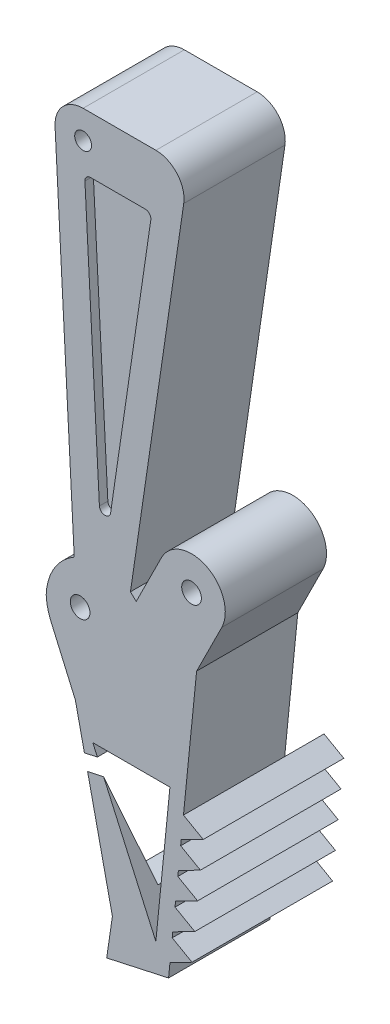
SolidWorks part; units mm, degrees
ref_plane "Front Plane" through (0, 0, 0) normal (0, 0, 1) x (1, 0, 0)
ref_plane "Top Plane" through (0, 0, 0) normal (0, 1, 0) x (1, 0, 0)
ref_plane "Right Plane" through (0, 0, 0) normal (1, 0, 0) x (0, 0, -1)
sketch "Sketch1" plane through (0, 0, 0) normal (0, 0, 1) x (1, 0, 0)
  line L1 (2.4995, -2.6404) -> (12.8102, 67.6069)
  line L2 (-7.4946, -2.2955) -> (-11.1898, 67.6069)
  line L3 (-11.1898, 67.6069) -> (12.8102, 67.6069)
  line L4 (-7.2953, -24.2105) -> (-0.7118, -54.2105)
  line L5 (-12.4946, -2.2955) -> (-12.4946, -12.2955)
  line L6 (-12.4946, -12.2955) -> (-7.2953, -24.2105)
  line L11 (2.4995, -2.6404) -> (3.5233, -3.6137)
  line L12 (3.5233, -3.6137) -> (7.9885, 5.334)
  line L13 (14.2607, -8.9719) -> (18.7258, -0.0241)
  line L15 (-12.4946, -2.2955) -> (-7.4946, -2.2955)
  line L16 (-0.7118, -54.2105) -> (-1.7284, -61.1363)
  line L17 (-1.7284, -61.1363) -> (9.2716, -58.7224)
  line L18 (9.2716, -58.7224) -> (14.2607, -8.9719)
  arc A0 (18.7258, -0.0241) -> (7.9885, 5.334) centre (13.3571, 2.655) ccw
  point P9 (0, 0)
  dimension "D15" = 12
  dimension "D1" = 10
  dimension "D2" = 71
  dimension "D3" = 70
  dimension "D4" = 24
  dimension "D5" = 5
  dimension "D6" = 10
  dimension "D7" = 13
  dimension "D8" = 30
  dimension "D9" = 7
  dimension "D10" = 11
  dimension "D11" = 50
  dimension "D12" = 10
  dimension "D13" = 10
  dimension "D14" = 12
extrude "Boss-Extrude1" add sketch "Sketch1" along normal blind 18
sketch "Sketch4" plane through (0, 0, 0) normal (0, 0, -1) x (-1, 0, 0)
  line L0 (0.7118, -54.2105) -> (-14.7329, -54.2105) construction
  line L1 (-7.0105, -54.2105) -> (-9.5176, -29.2105)
  line L2 (-9.5176, -29.2105) -> (4.2008, -29.2105)
  line L3 (4.2008, -29.2105) -> (-7.0105, -54.2105)
  line L4 (-9.2716, -58.7224) -> (-14.2607, -8.9719) construction
  dimension "D1" = 25
  dimension "D2" = 13.7184
  dimension "D3" = 2.7
extrude "Cut-Extrude1" cut sketch "Sketch4" against normal blind 25
sketch "Sketch5" plane through (0, 0, 18) normal (0, 0, 1) x (1, 0, 0)
  line L1 (9.5235, -56.2105) -> (9.9246, -52.2105)
  line L2 (9.2716, -58.7224) -> (14.2607, -8.9719) construction
  line L3 (9.9246, -52.2105) -> (13.4409, -54.2105)
  line L4 (9.5235, -56.2105) -> (13.4409, -54.2105)
  point P8 (9.7241, -54.2105)
  dimension "D1" = 4
extrude "Boss-Extrude2" add sketch "Sketch5" against normal blind 25
pattern_linear "LPattern1" count 5 spacing 5 along (0.0998, 0.995, 0) of "Boss-Extrude2"
fillet "Fillet1" radius 10 2 edges at (-12.4946, -12.2955, 9) (-12.4946, -2.2955, 9)
fillet "Fillet2" radius 5 2 edges at (12.8102, 67.6069, 9) (-11.1898, 67.6069, 9)
sketch "Sketch6" plane through (0, 0, 18) normal (0, 0, 1) x (1, 0, 0)
  circle A0 centre (-5.9185, 62.6069) radius 1.5
  dimension "D1" = 3
extrude "Cut-Extrude2" cut sketch "Sketch6" against normal blind 25
sketch "Sketch7" plane through (-12.029, -2.6397, 0) normal (-0.9768, -0.2143, 0) x (0, 0, 1)
  line L0 (9, -22.0841) -> (9, -29.5841) construction
  line L1 (18, -22.0841) -> (0, -22.0841) construction
  line L7 (-0.5, -29.5841) -> (18.5, -29.5841)
  line L8 (9, -29.5841) -> (9, -51.7989) construction
  line L12 (15, -48.1409) -> (3, -48.1409)
  line L13 (-0.5, -29.5841) -> (3, -48.1409)
  line L14 (18.5, -29.5841) -> (15, -48.1409)
  point P9 (9, -43.6664)
  point P13 (9, -29.5841)
  point P14 (9, -48.1409)
  dimension "D1" = 19
  dimension "D2" = 7.5
  dimension "D4" = 12
extrude "Cut-Extrude3" cut sketch "Sketch7" against normal blind 8
sketch "Sketch8" plane through (0, 0, 18) normal (0, 0, 1) x (1, 0, 0)
  circle A0 centre (13.3571, 2.655) radius 1.75
  dimension "D1" = 3.5
extrude "Cut-Extrude4" cut sketch "Sketch8" against normal blind 61
sketch "Sketch9" plane through (0, 0, 0) normal (0, 0, -1) x (-1, 0, 0)
  circle A1 centre (6.4528, -9.4872) radius 1.75
  dimension "D1" = 3.5
extrude "Cut-Extrude5" cut sketch "Sketch9" against normal blind 25
sketch "Sketch10" plane through (0, 0, 0) normal (0, 0, -1) x (-1, 0, 0)
  line L0 (-5.1313, 57.6069) -> (4.6, 57.6069)
  line L1 (-6.1207, 56.4617) -> (1.0338, 7.7175)
  line L2 (3.0218, 7.8099) -> (5.5986, 56.5541)
  line L3 (-2.4995, -2.6404) -> (-11.9697, 61.8808) construction
  line L4 (10.9116, 62.343) -> (7.4946, -2.2955) construction
  line L5 (-7.0227, 67.6069) -> (5.9185, 67.6069) construction
  arc A0 (3.0218, 7.8099) -> (1.0338, 7.7175) centre (2.0232, 7.8627) cw
  arc A1 (5.5986, 56.5541) -> (4.6, 57.6069) centre (4.6, 56.6069) ccw
  arc A2 (-5.1313, 57.6069) -> (-6.1207, 56.4617) centre (-5.1313, 56.6069) ccw
  dimension "D4" = 1
  dimension "D1" = 5
  dimension "D2" = 5
  dimension "D3" = 10
extrude "Cut-Extrude6" cut sketch "Sketch10" against normal blind 1.5
ref_plane "Plane1" through (0, 0, 9) normal (0, 0, -1) x (-1, 0, 0)
mirror "Mirror1" about plane through (0, 0, 9) normal (0, 0, -1) of "Cut-Extrude6"
